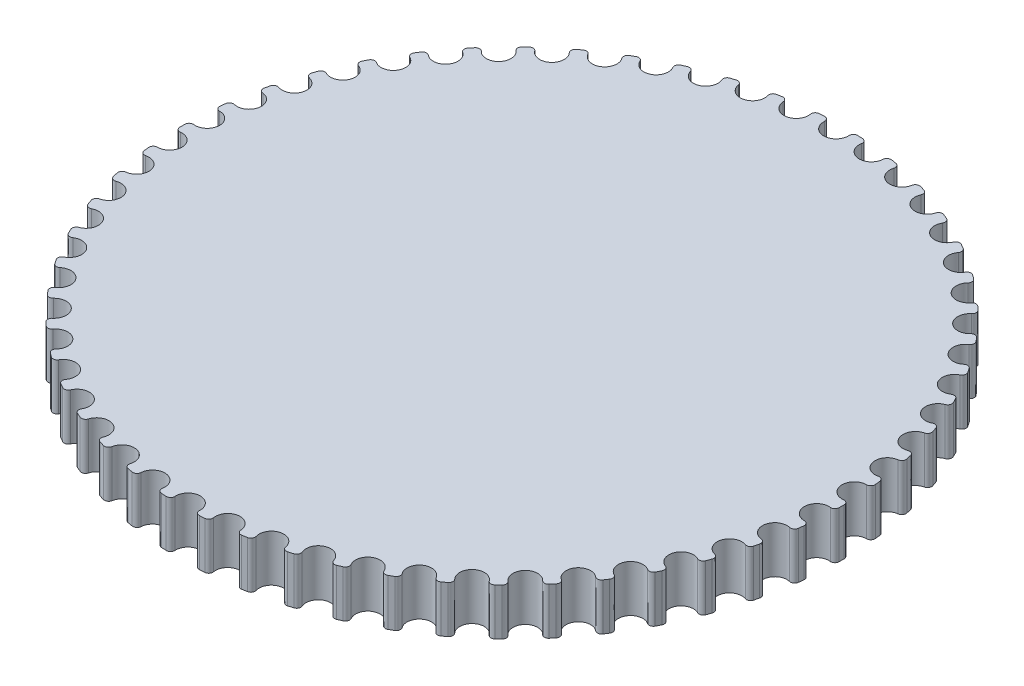
SolidWorks part; units mm, degrees
ref_plane "Front Plane" through (0, 0, 0) normal (0, 0, 1) x (1, 0, 0)
ref_plane "Top Plane" through (0, 0, 0) normal (0, 1, 0) x (1, 0, 0)
ref_plane "Right Plane" through (0, 0, 0) normal (1, 0, 0) x (0, 0, -1)
sketch "Sketch1" plane through (0, 0, 0) normal (0, 1, 0) x (1, 0, 0)
  line L0 (0, 0) -> (42.2106, 0) construction
  line L1 (0, 0) -> (42.1392, 2.4543) construction
  circle A0 centre (0, 0) radius 42.2106 construction
  arc A1 (41.4307, 3.9878) -> (41.6135, 0.849) centre (41.4292, 2.413) ccw
  arc A2 (41.6135, 0.849) -> (42.2093, 0.3234) centre (41.676, 0.3193) cw
  arc A3 (42.2093, 0.3234) -> (42.2106, 0) centre (0, 0) cw
  arc A4 (41.4307, 3.9878) -> (41.9615, 4.579) centre (41.4312, 4.5212) ccw
  arc A5 (41.9615, 4.579) -> (41.9252, 4.9003) centre (0, 0) ccw
  arc A6 (41.9615, -4.579) -> (41.9252, -4.9003) centre (0, 0) cw
  arc A7 (41.4307, -3.9878) -> (41.9615, -4.579) centre (41.4312, -4.5212) cw
  arc A8 (41.6135, -0.849) -> (41.4307, -3.9878) centre (41.4292, -2.413) ccw
  arc A9 (41.6135, -0.849) -> (42.2093, -0.3234) centre (41.676, -0.3193) ccw
  arc A10 (42.2093, -0.3234) -> (42.2106, 0) centre (0, 0) ccw
  arc A11 (41.1462, -9.4195) -> (41.0728, -9.7344) centre (0, 0) cw
  arc A12 (40.6876, -8.7706) -> (41.1462, -9.4195) centre (40.6262, -9.3005) cw
  arc A13 (41.2336, -5.6743) -> (40.6876, -8.7706) centre (40.8689, -7.2063) ccw
  arc A14 (41.2336, -5.6743) -> (41.8864, -5.2214) centre (41.3571, -5.1554) ccw
  arc A15 (41.8864, -5.2214) -> (41.9252, -4.9003) centre (0, 0) ccw
  arc A16 (39.7744, -14.1326) -> (39.665, -14.4369) centre (0, 0) cw
  arc A17 (39.3943, -13.4349) -> (39.7744, -14.1326) centre (39.2718, -13.954) cw
  arc A18 (40.296, -10.4229) -> (39.3943, -13.4349) centre (39.756, -11.9022) ccw
  arc A19 (40.296, -10.4229) -> (40.997, -10.0488) centre (40.479, -9.9218) ccw
  arc A20 (40.997, -10.0488) -> (41.0728, -9.7344) centre (0, 0) ccw
  arc A21 (37.8648, -18.6546) -> (37.7208, -18.9441) centre (0, 0) cw
  arc A22 (37.5682, -17.9174) -> (37.8648, -18.6546) centre (37.3863, -18.4188) cw
  arc A23 (38.8135, -15.0305) -> (37.5682, -17.9174) centre (38.1054, -16.4371) ccw
  arc A24 (38.8135, -15.0305) -> (39.5532, -14.7403) centre (39.0534, -14.554) ccw
  arc A25 (39.5532, -14.7403) -> (39.665, -14.4369) centre (0, 0) ccw
  arc A26 (35.4431, -22.9243) -> (35.2664, -23.1951) centre (0, 0) cw
  arc A27 (35.2341, -22.1577) -> (35.4431, -22.9243) centre (34.9952, -22.6346) cw
  arc A28 (36.8062, -19.4348) -> (35.2341, -22.1577) centre (35.9395, -20.7497) ccw
  arc A29 (36.8062, -19.4348) -> (37.5745, -19.2325) centre (37.0997, -18.9894) ccw
  arc A30 (37.5745, -19.2325) -> (37.7208, -18.9441) centre (0, 0) ccw
  arc A31 (32.5421, -26.8839) -> (32.3352, -27.1324) centre (0, 0) cw
  arc A32 (32.4235, -26.0983) -> (32.5421, -26.8839) centre (32.1309, -26.5442) cw
  arc A33 (34.3011, -23.5763) -> (32.4235, -26.0983) centre (33.2876, -24.7817) ccw
  arc A34 (34.3011, -23.5763) -> (35.0877, -23.4646) centre (34.6443, -23.1681) ccw
  arc A35 (35.0877, -23.4646) -> (35.2664, -23.1951) centre (0, 0) ccw
  arc A36 (29.201, -30.4801) -> (28.9667, -30.7029) centre (0, 0) cw
  arc A37 (29.1745, -29.686) -> (29.201, -30.4801) centre (28.832, -30.0949) cw
  arc A38 (31.3321, -27.399) -> (29.1745, -29.686) centre (30.1856, -28.4786) ccw
  arc A39 (31.3321, -27.399) -> (32.1264, -27.3793) centre (31.7204, -27.0334) ccw
  arc A40 (32.1264, -27.3793) -> (32.3352, -27.1324) centre (0, 0) ccw
  arc A41 (25.465, -33.664) -> (25.2064, -33.8581) centre (0, 0) cw
  arc A42 (25.5309, -32.8722) -> (25.465, -33.664) centre (25.1433, -33.2386) cw
  arc A43 (27.9394, -30.8512) -> (25.5309, -32.8722) centre (26.6753, -31.7904) ccw
  arc A44 (27.9394, -30.8512) -> (28.7306, -30.9239) centre (28.3676, -30.5331) ccw
  arc A45 (28.7306, -30.9239) -> (28.9667, -30.7029) centre (0, 0) ccw
  arc A46 (21.3847, -36.3927) -> (21.1053, -36.5554) centre (0, 0) cw
  arc A47 (21.542, -35.6139) -> (21.3847, -36.3927) centre (21.1145, -35.9328) cw
  arc A48 (24.1689, -33.8862) -> (21.542, -35.6139) centre (22.8043, -34.6722) ccw
  arc A49 (24.1689, -33.8862) -> (24.9463, -34.0502) centre (24.6311, -33.6199) ccw
  arc A50 (24.9463, -34.0502) -> (25.2064, -33.8581) centre (0, 0) ccw
  arc A51 (17.0152, -38.6292) -> (16.7188, -38.7584) centre (0, 0) cw
  arc A52 (17.2618, -37.8739) -> (17.0152, -38.6292) centre (16.8002, -38.1411) cw
  arc A53 (20.0715, -36.4629) -> (17.2618, -37.8739) centre (18.6249, -37.0852) ccw
  arc A54 (20.0715, -36.4629) -> (20.8246, -36.716) centre (20.5615, -36.2521) ccw
  arc A55 (20.8246, -36.716) -> (21.1053, -36.5554) centre (0, 0) ccw
  arc A56 (12.4155, -40.3434) -> (12.1061, -40.4373) centre (0, 0) cw
  arc A57 (12.7482, -39.6218) -> (12.4155, -40.3434) centre (12.2587, -39.8336) cw
  arc A58 (15.7027, -38.5465) -> (12.7482, -39.6218) centre (14.1936, -38.9967) ccw
  arc A59 (15.7027, -38.5465) -> (16.4214, -38.8854) centre (16.2138, -38.394) ccw
  arc A60 (16.4214, -38.8854) -> (16.7188, -38.7584) centre (0, 0) ccw
  arc A61 (7.648, -41.5119) -> (7.3298, -41.5693) centre (0, 0) cw
  arc A62 (8.0622, -40.8339) -> (7.648, -41.5119) centre (7.5514, -40.9874) cw
  arc A63 (11.1216, -40.1088) -> (8.0622, -40.8339) centre (9.5704, -40.3808) ccw
  arc A64 (11.1216, -40.1088) -> (11.796, -40.5288) centre (11.6469, -40.0167) ccw
  arc A65 (11.796, -40.5288) -> (12.1061, -40.4373) centre (0, 0) ccw
  arc A66 (2.7771, -42.1191) -> (2.4543, -42.1392) centre (0, 0) cw
  arc A67 (3.2672, -41.4938) -> (2.7771, -42.1191) centre (2.742, -41.5869) cw
  arc A68 (6.39, -41.1287) -> (3.2672, -41.4938) centre (4.8178, -41.2188) ccw
  arc A69 (6.39, -41.1287) -> (7.0111, -41.6242) centre (6.9225, -41.0982) ccw
  arc A70 (7.0111, -41.6242) -> (7.3298, -41.5693) centre (0, 0) ccw
  arc A71 (-2.1314, -42.1567) -> (-2.4543, -42.1392) centre (0, 0) cw
  arc A72 (-1.572, -41.5925) -> (-2.1314, -42.1567) centre (-2.1045, -41.624) cw
  arc A73 (1.572, -41.5925) -> (-1.572, -41.5925) centre (0, -41.4994) ccw
  arc A74 (1.572, -41.5925) -> (2.1314, -42.1567) centre (2.1045, -41.624) ccw
  arc A75 (2.1314, -42.1567) -> (2.4543, -42.1392) centre (0, 0) ccw
  arc A76 (-7.0111, -41.6242) -> (-7.3298, -41.5693) centre (0, 0) cw
  arc A77 (-6.39, -41.1287) -> (-7.0111, -41.6242) centre (-6.9225, -41.0982) cw
  arc A78 (-3.2672, -41.4938) -> (-6.39, -41.1287) centre (-4.8178, -41.2188) ccw
  arc A79 (-3.2672, -41.4938) -> (-2.7771, -42.1191) centre (-2.742, -41.5869) ccw
  arc A80 (-2.7771, -42.1191) -> (-2.4543, -42.1392) centre (0, 0) ccw
  arc A81 (-11.796, -40.5288) -> (-12.1061, -40.4373) centre (0, 0) cw
  arc A82 (-11.1216, -40.1088) -> (-11.796, -40.5288) centre (-11.6469, -40.0167) cw
  arc A83 (-8.0622, -40.8339) -> (-11.1216, -40.1088) centre (-9.5704, -40.3808) ccw
  arc A84 (-8.0622, -40.8339) -> (-7.648, -41.5119) centre (-7.5514, -40.9874) ccw
  arc A85 (-7.648, -41.5119) -> (-7.3298, -41.5693) centre (0, 0) ccw
  arc A86 (-16.4214, -38.8854) -> (-16.7188, -38.7584) centre (0, 0) cw
  arc A87 (-15.7027, -38.5465) -> (-16.4214, -38.8854) centre (-16.2138, -38.394) cw
  arc A88 (-12.7482, -39.6218) -> (-15.7027, -38.5465) centre (-14.1936, -38.9967) ccw
  arc A89 (-12.7482, -39.6218) -> (-12.4155, -40.3434) centre (-12.2587, -39.8336) ccw
  arc A90 (-12.4155, -40.3434) -> (-12.1061, -40.4373) centre (0, 0) ccw
  arc A91 (-20.8246, -36.716) -> (-21.1053, -36.5554) centre (0, 0) cw
  arc A92 (-20.0715, -36.4629) -> (-20.8246, -36.716) centre (-20.5615, -36.2521) cw
  arc A93 (-17.2618, -37.8739) -> (-20.0715, -36.4629) centre (-18.6249, -37.0852) ccw
  arc A94 (-17.2618, -37.8739) -> (-17.0152, -38.6292) centre (-16.8002, -38.1411) ccw
  arc A95 (-17.0152, -38.6292) -> (-16.7188, -38.7584) centre (0, 0) ccw
  arc A96 (-24.9463, -34.0502) -> (-25.2064, -33.8581) centre (0, 0) cw
  arc A97 (-24.1689, -33.8862) -> (-24.9463, -34.0502) centre (-24.6311, -33.6199) cw
  arc A98 (-21.542, -35.6139) -> (-24.1689, -33.8862) centre (-22.8043, -34.6722) ccw
  arc A99 (-21.542, -35.6139) -> (-21.3847, -36.3927) centre (-21.1145, -35.9328) ccw
  arc A100 (-21.3847, -36.3927) -> (-21.1053, -36.5554) centre (0, 0) ccw
  arc A101 (-28.7306, -30.9239) -> (-28.9667, -30.7029) centre (0, 0) cw
  arc A102 (-27.9394, -30.8512) -> (-28.7306, -30.9239) centre (-28.3676, -30.5331) cw
  arc A103 (-25.5309, -32.8722) -> (-27.9394, -30.8512) centre (-26.6753, -31.7904) ccw
  arc A104 (-25.5309, -32.8722) -> (-25.465, -33.664) centre (-25.1433, -33.2386) ccw
  arc A105 (-25.465, -33.664) -> (-25.2064, -33.8581) centre (0, 0) ccw
  arc A106 (-32.1264, -27.3793) -> (-32.3352, -27.1324) centre (0, 0) cw
  arc A107 (-31.3321, -27.399) -> (-32.1264, -27.3793) centre (-31.7204, -27.0334) cw
  arc A108 (-29.1745, -29.686) -> (-31.3321, -27.399) centre (-30.1856, -28.4786) ccw
  arc A109 (-29.1745, -29.686) -> (-29.201, -30.4801) centre (-28.832, -30.0949) ccw
  arc A110 (-29.201, -30.4801) -> (-28.9667, -30.7029) centre (0, 0) ccw
  arc A111 (-35.0877, -23.4646) -> (-35.2664, -23.1951) centre (0, 0) cw
  arc A112 (-34.3011, -23.5763) -> (-35.0877, -23.4646) centre (-34.6443, -23.1681) cw
  arc A113 (-32.4235, -26.0983) -> (-34.3011, -23.5763) centre (-33.2876, -24.7817) ccw
  arc A114 (-32.4235, -26.0983) -> (-32.5421, -26.8839) centre (-32.1309, -26.5442) ccw
  arc A115 (-32.5421, -26.8839) -> (-32.3352, -27.1324) centre (0, 0) ccw
  arc A116 (-37.5745, -19.2325) -> (-37.7208, -18.9441) centre (0, 0) cw
  arc A117 (-36.8062, -19.4348) -> (-37.5745, -19.2325) centre (-37.0997, -18.9894) cw
  arc A118 (-35.2341, -22.1577) -> (-36.8062, -19.4348) centre (-35.9395, -20.7497) ccw
  arc A119 (-35.2341, -22.1577) -> (-35.4431, -22.9243) centre (-34.9952, -22.6346) ccw
  arc A120 (-35.4431, -22.9243) -> (-35.2664, -23.1951) centre (0, 0) ccw
  arc A121 (-39.5532, -14.7403) -> (-39.665, -14.4369) centre (0, 0) cw
  arc A122 (-38.8135, -15.0305) -> (-39.5532, -14.7403) centre (-39.0534, -14.554) cw
  arc A123 (-37.5682, -17.9174) -> (-38.8135, -15.0305) centre (-38.1054, -16.4371) ccw
  arc A124 (-37.5682, -17.9174) -> (-37.8648, -18.6546) centre (-37.3863, -18.4188) ccw
  arc A125 (-37.8648, -18.6546) -> (-37.7208, -18.9441) centre (0, 0) ccw
  arc A126 (-40.997, -10.0488) -> (-41.0728, -9.7344) centre (0, 0) cw
  arc A127 (-40.296, -10.4229) -> (-40.997, -10.0488) centre (-40.479, -9.9218) cw
  arc A128 (-39.3943, -13.4349) -> (-40.296, -10.4229) centre (-39.756, -11.9022) ccw
  arc A129 (-39.3943, -13.4349) -> (-39.7744, -14.1326) centre (-39.2718, -13.954) ccw
  arc A130 (-39.7744, -14.1326) -> (-39.665, -14.4369) centre (0, 0) ccw
  arc A131 (-41.8864, -5.2214) -> (-41.9252, -4.9003) centre (0, 0) cw
  arc A132 (-41.2336, -5.6743) -> (-41.8864, -5.2214) centre (-41.3571, -5.1554) cw
  arc A133 (-40.6876, -8.7706) -> (-41.2336, -5.6743) centre (-40.8689, -7.2063) ccw
  arc A134 (-40.6876, -8.7706) -> (-41.1462, -9.4195) centre (-40.6262, -9.3005) ccw
  arc A135 (-41.1462, -9.4195) -> (-41.0728, -9.7344) centre (0, 0) ccw
  arc A136 (-42.2093, -0.3234) -> (-42.2106, 0) centre (0, 0) cw
  arc A137 (-41.6135, -0.849) -> (-42.2093, -0.3234) centre (-41.676, -0.3193) cw
  arc A138 (-41.4307, -3.9878) -> (-41.6135, -0.849) centre (-41.4292, -2.413) ccw
  arc A139 (-41.4307, -3.9878) -> (-41.9615, -4.579) centre (-41.4312, -4.5212) ccw
  arc A140 (-41.9615, -4.579) -> (-41.9252, -4.9003) centre (0, 0) ccw
  arc A141 (-41.9615, 4.579) -> (-41.9252, 4.9003) centre (0, 0) cw
  arc A142 (-41.4307, 3.9878) -> (-41.9615, 4.579) centre (-41.4312, 4.5212) cw
  arc A143 (-41.6135, 0.849) -> (-41.4307, 3.9878) centre (-41.4292, 2.413) ccw
  arc A144 (-41.6135, 0.849) -> (-42.2093, 0.3234) centre (-41.676, 0.3193) ccw
  arc A145 (-42.2093, 0.3234) -> (-42.2106, 0) centre (0, 0) ccw
  arc A146 (-41.1462, 9.4195) -> (-41.0728, 9.7344) centre (0, 0) cw
  arc A147 (-40.6876, 8.7706) -> (-41.1462, 9.4195) centre (-40.6262, 9.3005) cw
  arc A148 (-41.2336, 5.6743) -> (-40.6876, 8.7706) centre (-40.8689, 7.2063) ccw
  arc A149 (-41.2336, 5.6743) -> (-41.8864, 5.2214) centre (-41.3571, 5.1554) ccw
  arc A150 (-41.8864, 5.2214) -> (-41.9252, 4.9003) centre (0, 0) ccw
  arc A151 (-39.7744, 14.1326) -> (-39.665, 14.4369) centre (0, 0) cw
  arc A152 (-39.3943, 13.4349) -> (-39.7744, 14.1326) centre (-39.2718, 13.954) cw
  arc A153 (-40.296, 10.4229) -> (-39.3943, 13.4349) centre (-39.756, 11.9022) ccw
  arc A154 (-40.296, 10.4229) -> (-40.997, 10.0488) centre (-40.479, 9.9218) ccw
  arc A155 (-40.997, 10.0488) -> (-41.0728, 9.7344) centre (0, 0) ccw
  arc A156 (-37.8648, 18.6546) -> (-37.7208, 18.9441) centre (0, 0) cw
  arc A157 (-37.5682, 17.9174) -> (-37.8648, 18.6546) centre (-37.3863, 18.4188) cw
  arc A158 (-38.8135, 15.0305) -> (-37.5682, 17.9174) centre (-38.1054, 16.4371) ccw
  arc A159 (-38.8135, 15.0305) -> (-39.5532, 14.7403) centre (-39.0534, 14.554) ccw
  arc A160 (-39.5532, 14.7403) -> (-39.665, 14.4369) centre (0, 0) ccw
  arc A161 (-35.4431, 22.9243) -> (-35.2664, 23.1951) centre (0, 0) cw
  arc A162 (-35.2341, 22.1577) -> (-35.4431, 22.9243) centre (-34.9952, 22.6346) cw
  arc A163 (-36.8062, 19.4348) -> (-35.2341, 22.1577) centre (-35.9395, 20.7497) ccw
  arc A164 (-36.8062, 19.4348) -> (-37.5745, 19.2325) centre (-37.0997, 18.9894) ccw
  arc A165 (-37.5745, 19.2325) -> (-37.7208, 18.9441) centre (0, 0) ccw
  arc A166 (-32.5421, 26.8839) -> (-32.3352, 27.1324) centre (0, 0) cw
  arc A167 (-32.4235, 26.0983) -> (-32.5421, 26.8839) centre (-32.1309, 26.5442) cw
  arc A168 (-34.3011, 23.5763) -> (-32.4235, 26.0983) centre (-33.2876, 24.7817) ccw
  arc A169 (-34.3011, 23.5763) -> (-35.0877, 23.4646) centre (-34.6443, 23.1681) ccw
  arc A170 (-35.0877, 23.4646) -> (-35.2664, 23.1951) centre (0, 0) ccw
  arc A171 (-29.201, 30.4801) -> (-28.9667, 30.7029) centre (0, 0) cw
  arc A172 (-29.1745, 29.686) -> (-29.201, 30.4801) centre (-28.832, 30.0949) cw
  arc A173 (-31.3321, 27.399) -> (-29.1745, 29.686) centre (-30.1856, 28.4786) ccw
  arc A174 (-31.3321, 27.399) -> (-32.1264, 27.3793) centre (-31.7204, 27.0334) ccw
  arc A175 (-32.1264, 27.3793) -> (-32.3352, 27.1324) centre (0, 0) ccw
  arc A176 (-25.465, 33.664) -> (-25.2064, 33.8581) centre (0, 0) cw
  arc A177 (-25.5309, 32.8722) -> (-25.465, 33.664) centre (-25.1433, 33.2386) cw
  arc A178 (-27.9394, 30.8512) -> (-25.5309, 32.8722) centre (-26.6753, 31.7904) ccw
  arc A179 (-27.9394, 30.8512) -> (-28.7306, 30.9239) centre (-28.3676, 30.5331) ccw
  arc A180 (-28.7306, 30.9239) -> (-28.9667, 30.7029) centre (0, 0) ccw
  arc A181 (-21.3847, 36.3927) -> (-21.1053, 36.5554) centre (0, 0) cw
  arc A182 (-21.542, 35.6139) -> (-21.3847, 36.3927) centre (-21.1145, 35.9328) cw
  arc A183 (-24.1689, 33.8862) -> (-21.542, 35.6139) centre (-22.8043, 34.6722) ccw
  arc A184 (-24.1689, 33.8862) -> (-24.9463, 34.0502) centre (-24.6311, 33.6199) ccw
  arc A185 (-24.9463, 34.0502) -> (-25.2064, 33.8581) centre (0, 0) ccw
  arc A186 (-17.0152, 38.6292) -> (-16.7188, 38.7584) centre (0, 0) cw
  arc A187 (-17.2618, 37.8739) -> (-17.0152, 38.6292) centre (-16.8002, 38.1411) cw
  arc A188 (-20.0715, 36.4629) -> (-17.2618, 37.8739) centre (-18.6249, 37.0852) ccw
  arc A189 (-20.0715, 36.4629) -> (-20.8246, 36.716) centre (-20.5615, 36.2521) ccw
  arc A190 (-20.8246, 36.716) -> (-21.1053, 36.5554) centre (0, 0) ccw
  arc A191 (-12.4155, 40.3434) -> (-12.1061, 40.4373) centre (0, 0) cw
  arc A192 (-12.7482, 39.6218) -> (-12.4155, 40.3434) centre (-12.2587, 39.8336) cw
  arc A193 (-15.7027, 38.5465) -> (-12.7482, 39.6218) centre (-14.1936, 38.9967) ccw
  arc A194 (-15.7027, 38.5465) -> (-16.4214, 38.8854) centre (-16.2138, 38.394) ccw
  arc A195 (-16.4214, 38.8854) -> (-16.7188, 38.7584) centre (0, 0) ccw
  arc A196 (-7.648, 41.5119) -> (-7.3298, 41.5693) centre (0, 0) cw
  arc A197 (-8.0622, 40.8339) -> (-7.648, 41.5119) centre (-7.5514, 40.9874) cw
  arc A198 (-11.1216, 40.1088) -> (-8.0622, 40.8339) centre (-9.5704, 40.3808) ccw
  arc A199 (-11.1216, 40.1088) -> (-11.796, 40.5288) centre (-11.6469, 40.0167) ccw
  arc A200 (-11.796, 40.5288) -> (-12.1061, 40.4373) centre (0, 0) ccw
  arc A201 (-2.7771, 42.1191) -> (-2.4543, 42.1392) centre (0, 0) cw
  arc A202 (-3.2672, 41.4938) -> (-2.7771, 42.1191) centre (-2.742, 41.5869) cw
  arc A203 (-6.39, 41.1287) -> (-3.2672, 41.4938) centre (-4.8178, 41.2188) ccw
  arc A204 (-6.39, 41.1287) -> (-7.0111, 41.6242) centre (-6.9225, 41.0982) ccw
  arc A205 (-7.0111, 41.6242) -> (-7.3298, 41.5693) centre (0, 0) ccw
  arc A206 (2.1314, 42.1567) -> (2.4543, 42.1392) centre (0, 0) cw
  arc A207 (1.572, 41.5925) -> (2.1314, 42.1567) centre (2.1045, 41.624) cw
  arc A208 (-1.572, 41.5925) -> (1.572, 41.5925) centre (0, 41.4994) ccw
  arc A209 (-1.572, 41.5925) -> (-2.1314, 42.1567) centre (-2.1045, 41.624) ccw
  arc A210 (-2.1314, 42.1567) -> (-2.4543, 42.1392) centre (0, 0) ccw
  arc A211 (7.0111, 41.6242) -> (7.3298, 41.5693) centre (0, 0) cw
  arc A212 (6.39, 41.1287) -> (7.0111, 41.6242) centre (6.9225, 41.0982) cw
  arc A213 (3.2672, 41.4938) -> (6.39, 41.1287) centre (4.8178, 41.2188) ccw
  arc A214 (3.2672, 41.4938) -> (2.7771, 42.1191) centre (2.742, 41.5869) ccw
  arc A215 (2.7771, 42.1191) -> (2.4543, 42.1392) centre (0, 0) ccw
  arc A216 (11.796, 40.5288) -> (12.1061, 40.4373) centre (0, 0) cw
  arc A217 (11.1216, 40.1088) -> (11.796, 40.5288) centre (11.6469, 40.0167) cw
  arc A218 (8.0622, 40.8339) -> (11.1216, 40.1088) centre (9.5704, 40.3808) ccw
  arc A219 (8.0622, 40.8339) -> (7.648, 41.5119) centre (7.5514, 40.9874) ccw
  arc A220 (7.648, 41.5119) -> (7.3298, 41.5693) centre (0, 0) ccw
  arc A221 (16.4214, 38.8854) -> (16.7188, 38.7584) centre (0, 0) cw
  arc A222 (15.7027, 38.5465) -> (16.4214, 38.8854) centre (16.2138, 38.394) cw
  arc A223 (12.7482, 39.6218) -> (15.7027, 38.5465) centre (14.1936, 38.9967) ccw
  arc A224 (12.7482, 39.6218) -> (12.4155, 40.3434) centre (12.2587, 39.8336) ccw
  arc A225 (12.4155, 40.3434) -> (12.1061, 40.4373) centre (0, 0) ccw
  arc A226 (20.8246, 36.716) -> (21.1053, 36.5554) centre (0, 0) cw
  arc A227 (20.0715, 36.4629) -> (20.8246, 36.716) centre (20.5615, 36.2521) cw
  arc A228 (17.2618, 37.8739) -> (20.0715, 36.4629) centre (18.6249, 37.0852) ccw
  arc A229 (17.2618, 37.8739) -> (17.0152, 38.6292) centre (16.8002, 38.1411) ccw
  arc A230 (17.0152, 38.6292) -> (16.7188, 38.7584) centre (0, 0) ccw
  arc A231 (24.9463, 34.0502) -> (25.2064, 33.8581) centre (0, 0) cw
  arc A232 (24.1689, 33.8862) -> (24.9463, 34.0502) centre (24.6311, 33.6199) cw
  arc A233 (21.542, 35.6139) -> (24.1689, 33.8862) centre (22.8043, 34.6722) ccw
  arc A234 (21.542, 35.6139) -> (21.3847, 36.3927) centre (21.1145, 35.9328) ccw
  arc A235 (21.3847, 36.3927) -> (21.1053, 36.5554) centre (0, 0) ccw
  arc A236 (28.7306, 30.9239) -> (28.9667, 30.7029) centre (0, 0) cw
  arc A237 (27.9394, 30.8512) -> (28.7306, 30.9239) centre (28.3676, 30.5331) cw
  arc A238 (25.5309, 32.8722) -> (27.9394, 30.8512) centre (26.6753, 31.7904) ccw
  arc A239 (25.5309, 32.8722) -> (25.465, 33.664) centre (25.1433, 33.2386) ccw
  arc A240 (25.465, 33.664) -> (25.2064, 33.8581) centre (0, 0) ccw
  arc A241 (32.1264, 27.3793) -> (32.3352, 27.1324) centre (0, 0) cw
  arc A242 (31.3321, 27.399) -> (32.1264, 27.3793) centre (31.7204, 27.0334) cw
  arc A243 (29.1745, 29.686) -> (31.3321, 27.399) centre (30.1856, 28.4786) ccw
  arc A244 (29.1745, 29.686) -> (29.201, 30.4801) centre (28.832, 30.0949) ccw
  arc A245 (29.201, 30.4801) -> (28.9667, 30.7029) centre (0, 0) ccw
  arc A246 (35.0877, 23.4646) -> (35.2664, 23.1951) centre (0, 0) cw
  arc A247 (34.3011, 23.5763) -> (35.0877, 23.4646) centre (34.6443, 23.1681) cw
  arc A248 (32.4235, 26.0983) -> (34.3011, 23.5763) centre (33.2876, 24.7817) ccw
  arc A249 (32.4235, 26.0983) -> (32.5421, 26.8839) centre (32.1309, 26.5442) ccw
  arc A250 (32.5421, 26.8839) -> (32.3352, 27.1324) centre (0, 0) ccw
  arc A251 (37.5745, 19.2325) -> (37.7208, 18.9441) centre (0, 0) cw
  arc A252 (36.8062, 19.4348) -> (37.5745, 19.2325) centre (37.0997, 18.9894) cw
  arc A253 (35.2341, 22.1577) -> (36.8062, 19.4348) centre (35.9395, 20.7497) ccw
  arc A254 (35.2341, 22.1577) -> (35.4431, 22.9243) centre (34.9952, 22.6346) ccw
  arc A255 (35.4431, 22.9243) -> (35.2664, 23.1951) centre (0, 0) ccw
  arc A256 (39.5532, 14.7403) -> (39.665, 14.4369) centre (0, 0) cw
  arc A257 (38.8135, 15.0305) -> (39.5532, 14.7403) centre (39.0534, 14.554) cw
  arc A258 (37.5682, 17.9174) -> (38.8135, 15.0305) centre (38.1054, 16.4371) ccw
  arc A259 (37.5682, 17.9174) -> (37.8648, 18.6546) centre (37.3863, 18.4188) ccw
  arc A260 (37.8648, 18.6546) -> (37.7208, 18.9441) centre (0, 0) ccw
  arc A261 (40.997, 10.0488) -> (41.0728, 9.7344) centre (0, 0) cw
  arc A262 (40.296, 10.4229) -> (40.997, 10.0488) centre (40.479, 9.9218) cw
  arc A263 (39.3943, 13.4349) -> (40.296, 10.4229) centre (39.756, 11.9022) ccw
  arc A264 (39.3943, 13.4349) -> (39.7744, 14.1326) centre (39.2718, 13.954) ccw
  arc A265 (39.7744, 14.1326) -> (39.665, 14.4369) centre (0, 0) ccw
  arc A266 (41.8864, 5.2214) -> (41.9252, 4.9003) centre (0, 0) cw
  arc A267 (41.2336, 5.6743) -> (41.8864, 5.2214) centre (41.3571, 5.1554) cw
  arc A268 (40.6876, 8.7706) -> (41.2336, 5.6743) centre (40.8689, 7.2063) ccw
  arc A269 (40.6876, 8.7706) -> (41.1462, 9.4195) centre (40.6262, 9.3005) ccw
  arc A270 (41.1462, 9.4195) -> (41.0728, 9.7344) centre (0, 0) ccw
  point P23 (39.857, 2.3214)
  point P44 (0, 0)
  dimension "D1" = 84.4212
  dimension "D3" = 1.5748
  dimension "D4" = 0.5334
  dimension "D2" = 3.333
  dimension "D5" = 2.286
  dimension "D6" = 54
extrude "Boss-Extrude1" add sketch "Sketch1" along normal blind 6 contours A79 A80 A71 A72 A73 A74 A75 A66 A67 A68 A69 A70 A61 A62 A63 A64 A65 A56 A57 A58 A59 A60 A51 A52 A53 A54 A55 A46 A47 A48 A49 A50 A41 A42 A43 A44 A45 A36 A37 A38 A39 A40 A31 A32 A33 A34 A35 A26 A27 A28 A29 region at (0, 0, 0)
sketch "BeltOuterFace" plane through (0, 0, 0) normal (0, 1, 0) x (1, 0, 0)
  circle A0 centre (0, 0) radius 43.8418 construction
  dimension "D1" = 87.6837
equation "\"T\" = 54"
equation "\"P\"= 5mm"
equation "\"TanD\"= \"PD\" - \"BeltWidth\" * \"BeltWidthTune\""
equation "\"Angle\"= 360 / \"T\""
equation "\"D1@Sketch1\"=\"TanD\""
equation "\"D2@Sketch1\"=\"Angle\"/2"
equation "\"D6@Sketch1\"=\"T\""
equation "\"W\"= 6mm"
equation "\"D1@Boss-Extrude1\"=\"W\""
equation "\"PD\"= \"T\" * \"P\" / PI"
equation "\"BeltWidth\"= 1.74mm"
equation "\"BeltWidthTune\" = .875"
equation "\"D1@BeltOuterFace\"=\"PD\" + \"BeltWidth\""
